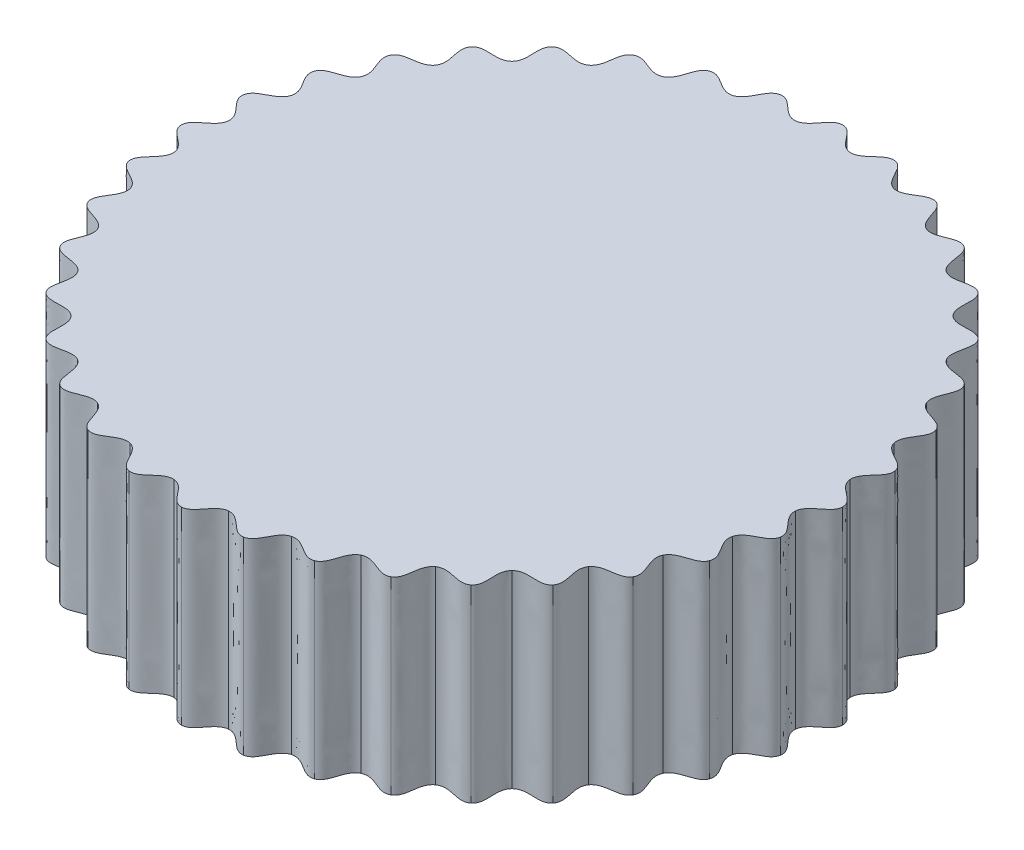
SolidWorks part; units mm, degrees
ref_plane "Front Plane" through (0, 0, 0) normal (0, 0, 1) x (1, 0, 0)
ref_plane "Top Plane" through (0, 0, 0) normal (0, 1, 0) x (1, 0, 0)
ref_plane "Right Plane" through (0, 0, 0) normal (1, 0, 0) x (0, 0, -1)
sketch "Sketch1" plane through (0, 0, 0) normal (0, 1, 0) x (1, 0, 0)
  line L0 (0, 0) -> (0, 35) construction
  line L1 (0, 0) -> (3.0505, 34.8668) construction
  line L2 (-0.5, 35) -> (0.5, 35) construction
  line L3 (3.3742, 32.8308) -> (2.378, 32.918) construction
  line L4 (0, 35) -> (2.8761, 32.8744) construction
  circle A1 centre (0, 0) radius 35 construction
  circle A2 centre (0, 0) radius 33 construction
  spline S0 degree 3 poles (0, 35) (0.6252, 35.0076) (1.4383, 33.9012) (2.2504, 32.9388) (2.8761, 32.8744) knots 0 0 0 0 0.5 1 1 1 1
  spline S1 degree 3 poles (0, 35) (-0.6252, 35.0076) (-1.4383, 33.9012) (-2.2504, 32.9388) (-2.8761, 32.8744) knots 0 0 0 0 0.5 1 1 1 1
  spline S2 degree 3 poles (6.0777, 34.4683) (6.6947, 34.3671) (7.3033, 33.1364) (7.936, 32.0476) (8.541, 31.8756) knots 0 0 0 0 0.5 1 1 1 1
  spline S3 degree 3 poles (6.0777, 34.4683) (5.4633, 34.5843) (4.4704, 33.6359) (3.5035, 32.8292) (2.8761, 32.8744) knots 0 0 0 0 0.5 1 1 1 1
  spline S4 degree 3 poles (11.9707, 32.8892) (12.5608, 32.6825) (12.9465, 31.3648) (13.3805, 30.1827) (13.9464, 29.9082) knots 0 0 0 0 0.5 1 1 1 1
  spline S5 degree 3 poles (11.9707, 32.8892) (11.3858, 33.1102) (10.2433, 32.3487) (9.151, 31.7221) (8.541, 31.8756) knots 0 0 0 0 0.5 1 1 1 1
  spline S6 degree 3 poles (17.5, 30.3109) (18.0452, 30.0048) (18.1962, 28.6402) (18.4184, 27.4007) (18.928, 27.032) knots 0 0 0 0 0.5 1 1 1 1
  spline S7 degree 3 poles (17.5, 30.3109) (16.9623, 30.63) (15.705, 30.0785) (14.5205, 29.6511) (13.9464, 29.9082) knots 0 0 0 0 0.5 1 1 1 1
  spline S8 degree 3 poles (22.4976, 26.8116) (22.9814, 26.4155) (22.8931, 25.0453) (22.8966, 23.7861) (23.3345, 23.3345) knots 0 0 0 0 0.5 1 1 1 1
  spline S9 degree 3 poles (22.4976, 26.8116) (22.0235, 27.2192) (20.6895, 26.8944) (19.4488, 26.6792) (18.928, 27.032) knots 0 0 0 0 0.5 1 1 1 1
  spline S10 degree 3 poles (26.8116, 22.4976) (27.2192, 22.0235) (26.8944, 20.6895) (26.6792, 19.4488) (27.032, 18.928) knots 0 0 0 0 0.5 1 1 1 1
  spline S11 degree 3 poles (26.8116, 22.4976) (26.4155, 22.9814) (25.0453, 22.8931) (23.7861, 22.8966) (23.3345, 23.3345) knots 0 0 0 0 0.5 1 1 1 1
  spline S12 degree 3 poles (30.3109, 17.5) (30.63, 16.9623) (30.0785, 15.705) (29.6511, 14.5205) (29.9082, 13.9464) knots 0 0 0 0 0.5 1 1 1 1
  spline S13 degree 3 poles (30.3109, 17.5) (30.0048, 18.0452) (28.6402, 18.1962) (27.4007, 18.4184) (27.032, 18.928) knots 0 0 0 0 0.5 1 1 1 1
  spline S14 degree 3 poles (32.8892, 11.9707) (33.1102, 11.3858) (32.3487, 10.2433) (31.7221, 9.151) (31.8756, 8.541) knots 0 0 0 0 0.5 1 1 1 1
  spline S15 degree 3 poles (32.8892, 11.9707) (32.6825, 12.5608) (31.3648, 12.9465) (30.1827, 13.3805) (29.9082, 13.9464) knots 0 0 0 0 0.5 1 1 1 1
  spline S16 degree 3 poles (34.4683, 6.0777) (34.5843, 5.4633) (33.6359, 4.4704) (32.8292, 3.5035) (32.8744, 2.8761) knots 0 0 0 0 0.5 1 1 1 1
  spline S17 degree 3 poles (34.4683, 6.0777) (34.3671, 6.6947) (33.1364, 7.3033) (32.0476, 7.936) (31.8756, 8.541) knots 0 0 0 0 0.5 1 1 1 1
  spline S18 degree 3 poles (35, 0) (35.0076, -0.6252) (33.9012, -1.4383) (32.9388, -2.2504) (32.8744, -2.8761) knots 0 0 0 0 0.5 1 1 1 1
  spline S19 degree 3 poles (35, 0) (35.0076, 0.6252) (33.9012, 1.4383) (32.9388, 2.2504) (32.8744, 2.8761) knots 0 0 0 0 0.5 1 1 1 1
  spline S20 degree 3 poles (34.4683, -6.0777) (34.3671, -6.6947) (33.1364, -7.3033) (32.0476, -7.936) (31.8756, -8.541) knots 0 0 0 0 0.5 1 1 1 1
  spline S21 degree 3 poles (34.4683, -6.0777) (34.5843, -5.4633) (33.6359, -4.4704) (32.8292, -3.5035) (32.8744, -2.8761) knots 0 0 0 0 0.5 1 1 1 1
  spline S22 degree 3 poles (32.8892, -11.9707) (32.6825, -12.5608) (31.3648, -12.9465) (30.1827, -13.3805) (29.9082, -13.9464) knots 0 0 0 0 0.5 1 1 1 1
  spline S23 degree 3 poles (32.8892, -11.9707) (33.1102, -11.3858) (32.3487, -10.2433) (31.7221, -9.151) (31.8756, -8.541) knots 0 0 0 0 0.5 1 1 1 1
  spline S24 degree 3 poles (30.3109, -17.5) (30.0048, -18.0452) (28.6402, -18.1962) (27.4007, -18.4184) (27.032, -18.928) knots 0 0 0 0 0.5 1 1 1 1
  spline S25 degree 3 poles (30.3109, -17.5) (30.63, -16.9623) (30.0785, -15.705) (29.6511, -14.5205) (29.9082, -13.9464) knots 0 0 0 0 0.5 1 1 1 1
  spline S26 degree 3 poles (26.8116, -22.4976) (26.4155, -22.9814) (25.0453, -22.8931) (23.7861, -22.8966) (23.3345, -23.3345) knots 0 0 0 0 0.5 1 1 1 1
  spline S27 degree 3 poles (26.8116, -22.4976) (27.2192, -22.0235) (26.8944, -20.6895) (26.6792, -19.4488) (27.032, -18.928) knots 0 0 0 0 0.5 1 1 1 1
  spline S28 degree 3 poles (22.4976, -26.8116) (22.0235, -27.2192) (20.6895, -26.8944) (19.4488, -26.6792) (18.928, -27.032) knots 0 0 0 0 0.5 1 1 1 1
  spline S29 degree 3 poles (22.4976, -26.8116) (22.9814, -26.4155) (22.8931, -25.0453) (22.8966, -23.7861) (23.3345, -23.3345) knots 0 0 0 0 0.5 1 1 1 1
  spline S30 degree 3 poles (17.5, -30.3109) (16.9623, -30.63) (15.705, -30.0785) (14.5205, -29.6511) (13.9464, -29.9082) knots 0 0 0 0 0.5 1 1 1 1
  spline S31 degree 3 poles (17.5, -30.3109) (18.0452, -30.0048) (18.1962, -28.6402) (18.4184, -27.4007) (18.928, -27.032) knots 0 0 0 0 0.5 1 1 1 1
  spline S32 degree 3 poles (11.9707, -32.8892) (11.3858, -33.1102) (10.2433, -32.3487) (9.151, -31.7221) (8.541, -31.8756) knots 0 0 0 0 0.5 1 1 1 1
  spline S33 degree 3 poles (11.9707, -32.8892) (12.5608, -32.6825) (12.9465, -31.3648) (13.3805, -30.1827) (13.9464, -29.9082) knots 0 0 0 0 0.5 1 1 1 1
  spline S34 degree 3 poles (6.0777, -34.4683) (5.4633, -34.5843) (4.4704, -33.6359) (3.5035, -32.8292) (2.8761, -32.8744) knots 0 0 0 0 0.5 1 1 1 1
  spline S35 degree 3 poles (6.0777, -34.4683) (6.6947, -34.3671) (7.3033, -33.1364) (7.936, -32.0476) (8.541, -31.8756) knots 0 0 0 0 0.5 1 1 1 1
  spline S36 degree 3 poles (0, -35) (-0.6252, -35.0076) (-1.4383, -33.9012) (-2.2504, -32.9388) (-2.8761, -32.8744) knots 0 0 0 0 0.5 1 1 1 1
  spline S37 degree 3 poles (0, -35) (0.6252, -35.0076) (1.4383, -33.9012) (2.2504, -32.9388) (2.8761, -32.8744) knots 0 0 0 0 0.5 1 1 1 1
  spline S38 degree 3 poles (-6.0777, -34.4683) (-6.6947, -34.3671) (-7.3033, -33.1364) (-7.936, -32.0476) (-8.541, -31.8756) knots 0 0 0 0 0.5 1 1 1 1
  spline S39 degree 3 poles (-6.0777, -34.4683) (-5.4633, -34.5843) (-4.4704, -33.6359) (-3.5035, -32.8292) (-2.8761, -32.8744) knots 0 0 0 0 0.5 1 1 1 1
  spline S40 degree 3 poles (-11.9707, -32.8892) (-12.5608, -32.6825) (-12.9465, -31.3648) (-13.3805, -30.1827) (-13.9464, -29.9082) knots 0 0 0 0 0.5 1 1 1 1
  spline S41 degree 3 poles (-11.9707, -32.8892) (-11.3858, -33.1102) (-10.2433, -32.3487) (-9.151, -31.7221) (-8.541, -31.8756) knots 0 0 0 0 0.5 1 1 1 1
  spline S42 degree 3 poles (-17.5, -30.3109) (-18.0452, -30.0048) (-18.1962, -28.6402) (-18.4184, -27.4007) (-18.928, -27.032) knots 0 0 0 0 0.5 1 1 1 1
  spline S43 degree 3 poles (-17.5, -30.3109) (-16.9623, -30.63) (-15.705, -30.0785) (-14.5205, -29.6511) (-13.9464, -29.9082) knots 0 0 0 0 0.5 1 1 1 1
  spline S44 degree 3 poles (-22.4976, -26.8116) (-22.9814, -26.4155) (-22.8931, -25.0453) (-22.8966, -23.7861) (-23.3345, -23.3345) knots 0 0 0 0 0.5 1 1 1 1
  spline S45 degree 3 poles (-22.4976, -26.8116) (-22.0235, -27.2192) (-20.6895, -26.8944) (-19.4488, -26.6792) (-18.928, -27.032) knots 0 0 0 0 0.5 1 1 1 1
  spline S46 degree 3 poles (-26.8116, -22.4976) (-27.2192, -22.0235) (-26.8944, -20.6895) (-26.6792, -19.4488) (-27.032, -18.928) knots 0 0 0 0 0.5 1 1 1 1
  spline S47 degree 3 poles (-26.8116, -22.4976) (-26.4155, -22.9814) (-25.0453, -22.8931) (-23.7861, -22.8966) (-23.3345, -23.3345) knots 0 0 0 0 0.5 1 1 1 1
  spline S48 degree 3 poles (-30.3109, -17.5) (-30.63, -16.9623) (-30.0785, -15.705) (-29.6511, -14.5205) (-29.9082, -13.9464) knots 0 0 0 0 0.5 1 1 1 1
  spline S49 degree 3 poles (-30.3109, -17.5) (-30.0048, -18.0452) (-28.6402, -18.1962) (-27.4007, -18.4184) (-27.032, -18.928) knots 0 0 0 0 0.5 1 1 1 1
  spline S50 degree 3 poles (-32.8892, -11.9707) (-33.1102, -11.3858) (-32.3487, -10.2433) (-31.7221, -9.151) (-31.8756, -8.541) knots 0 0 0 0 0.5 1 1 1 1
  spline S51 degree 3 poles (-32.8892, -11.9707) (-32.6825, -12.5608) (-31.3648, -12.9465) (-30.1827, -13.3805) (-29.9082, -13.9464) knots 0 0 0 0 0.5 1 1 1 1
  spline S52 degree 3 poles (-34.4683, -6.0777) (-34.5843, -5.4633) (-33.6359, -4.4704) (-32.8292, -3.5035) (-32.8744, -2.8761) knots 0 0 0 0 0.5 1 1 1 1
  spline S53 degree 3 poles (-34.4683, -6.0777) (-34.3671, -6.6947) (-33.1364, -7.3033) (-32.0476, -7.936) (-31.8756, -8.541) knots 0 0 0 0 0.5 1 1 1 1
  spline S54 degree 3 poles (-35, 0) (-35.0076, 0.6252) (-33.9012, 1.4383) (-32.9388, 2.2504) (-32.8744, 2.8761) knots 0 0 0 0 0.5 1 1 1 1
  spline S55 degree 3 poles (-35, 0) (-35.0076, -0.6252) (-33.9012, -1.4383) (-32.9388, -2.2504) (-32.8744, -2.8761) knots 0 0 0 0 0.5 1 1 1 1
  spline S56 degree 3 poles (-34.4683, 6.0777) (-34.3671, 6.6947) (-33.1364, 7.3033) (-32.0476, 7.936) (-31.8756, 8.541) knots 0 0 0 0 0.5 1 1 1 1
  spline S57 degree 3 poles (-34.4683, 6.0777) (-34.5843, 5.4633) (-33.6359, 4.4704) (-32.8292, 3.5035) (-32.8744, 2.8761) knots 0 0 0 0 0.5 1 1 1 1
  spline S58 degree 3 poles (-32.8892, 11.9707) (-32.6825, 12.5608) (-31.3648, 12.9465) (-30.1827, 13.3805) (-29.9082, 13.9464) knots 0 0 0 0 0.5 1 1 1 1
  spline S59 degree 3 poles (-32.8892, 11.9707) (-33.1102, 11.3858) (-32.3487, 10.2433) (-31.7221, 9.151) (-31.8756, 8.541) knots 0 0 0 0 0.5 1 1 1 1
  spline S60 degree 3 poles (-30.3109, 17.5) (-30.0048, 18.0452) (-28.6402, 18.1962) (-27.4007, 18.4184) (-27.032, 18.928) knots 0 0 0 0 0.5 1 1 1 1
  spline S61 degree 3 poles (-30.3109, 17.5) (-30.63, 16.9623) (-30.0785, 15.705) (-29.6511, 14.5205) (-29.9082, 13.9464) knots 0 0 0 0 0.5 1 1 1 1
  spline S62 degree 3 poles (-26.8116, 22.4976) (-26.4155, 22.9814) (-25.0453, 22.8931) (-23.7861, 22.8966) (-23.3345, 23.3345) knots 0 0 0 0 0.5 1 1 1 1
  spline S63 degree 3 poles (-26.8116, 22.4976) (-27.2192, 22.0235) (-26.8944, 20.6895) (-26.6792, 19.4488) (-27.032, 18.928) knots 0 0 0 0 0.5 1 1 1 1
  spline S64 degree 3 poles (-22.4976, 26.8116) (-22.0235, 27.2192) (-20.6895, 26.8944) (-19.4488, 26.6792) (-18.928, 27.032) knots 0 0 0 0 0.5 1 1 1 1
  spline S65 degree 3 poles (-22.4976, 26.8116) (-22.9814, 26.4155) (-22.8931, 25.0453) (-22.8966, 23.7861) (-23.3345, 23.3345) knots 0 0 0 0 0.5 1 1 1 1
  spline S66 degree 3 poles (-17.5, 30.3109) (-16.9623, 30.63) (-15.705, 30.0785) (-14.5205, 29.6511) (-13.9464, 29.9082) knots 0 0 0 0 0.5 1 1 1 1
  spline S67 degree 3 poles (-17.5, 30.3109) (-18.0452, 30.0048) (-18.1962, 28.6402) (-18.4184, 27.4007) (-18.928, 27.032) knots 0 0 0 0 0.5 1 1 1 1
  spline S68 degree 3 poles (-11.9707, 32.8892) (-11.3858, 33.1102) (-10.2433, 32.3487) (-9.151, 31.7221) (-8.541, 31.8756) knots 0 0 0 0 0.5 1 1 1 1
  spline S69 degree 3 poles (-11.9707, 32.8892) (-12.5608, 32.6825) (-12.9465, 31.3648) (-13.3805, 30.1827) (-13.9464, 29.9082) knots 0 0 0 0 0.5 1 1 1 1
  spline S70 degree 3 poles (-6.0777, 34.4683) (-5.4633, 34.5843) (-4.4704, 33.6359) (-3.5035, 32.8292) (-2.8761, 32.8744) knots 0 0 0 0 0.5 1 1 1 1
  spline S71 degree 3 poles (-6.0777, 34.4683) (-6.6947, 34.3671) (-7.3033, 33.1364) (-7.936, 32.0476) (-8.541, 31.8756) knots 0 0 0 0 0.5 1 1 1 1
  point P4 (2.8761, 32.8744)
  point P9 (0, 35)
  point P13 (2.8761, 32.8744)
  point P196 (0, 0)
  dimension "D1" = 70
  dimension "D3" = 5
  dimension "D2" = 90
  dimension "D6" = 2
  dimension "D4" = 1
  dimension "D5" = 1
extrude "Boss-Extrude1" add sketch "Sketch1" along normal blind 20
